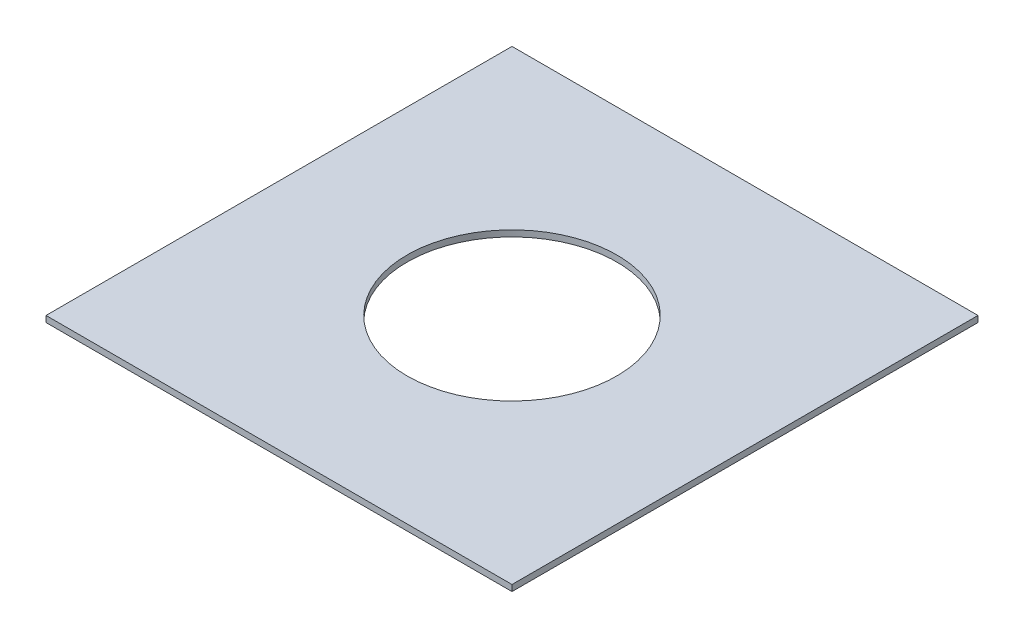
SolidWorks part; units mm, degrees
material "PTFE (general)"
ref_plane "Front Plane" through (0, 0, 0) normal (0, 0, 1) x (1, 0, 0)
ref_plane "Top Plane" through (0, 0, 0) normal (0, 1, 0) x (1, 0, 0)
ref_plane "Right Plane" through (0, 0, 0) normal (1, 0, 0) x (0, 0, -1)
sketch "Sketch1" plane through (0, 0, 0) normal (0, 1, 0) x (1, 0, 0)
  line L0 (17.5573, 30.5402) -> (17.5573, -29.4598) construction
  line L9 (17.5573, -29.4598) -> (77.5573, -29.4598) construction
  line L10 (77.5573, -29.4598) -> (77.5573, 30.5402) construction
  line L11 (17.5573, 30.5402) -> (77.5573, 30.5402) construction
  line L12 (17.5573, 30.5402) -> (17.5573, -29.4598)
  line L13 (17.5573, -29.4598) -> (77.5573, -29.4598)
  line L14 (77.5573, -29.4598) -> (77.5573, 30.5402)
  line L16 (17.5573, 30.5402) -> (77.5573, 30.5402)
  circle A2 centre (47.5573, 0.5402) radius 13.5
  circle A3 centre (47.5573, 0.5402) radius 13.5
  dimension "D1" = 0
extrude "Boss-Extrude1" add sketch "Sketch1" along normal blind 0.7937
